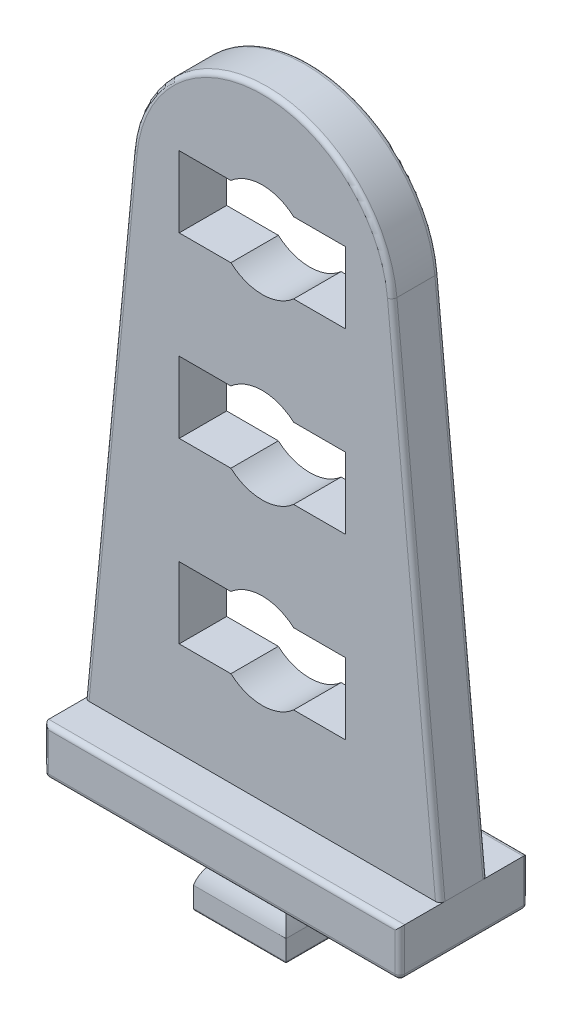
SolidWorks part; units mm, degrees
ref_plane "前视基准面" through (0, 0, 0) normal (0, 0, 1) x (1, 0, 0)
ref_plane "上视基准面" through (0, 0, 0) normal (0, 1, 0) x (1, 0, 0)
ref_plane "右视基准面" through (0, 0, 0) normal (1, 0, 0) x (0, 0, -1)
sketch "草图1" plane through (0, 0, 0) normal (0, 0, 1) x (1, 0, 0)
  line L0 (0, 0) -> (7.5, 0)
  line L1 (7.5, 0) -> (7.5, 2)
  line L2 (7.5, 2) -> (-7.5, 2)
  line L3 (-7.5, 2) -> (-7.5, 0)
  line L4 (-7.5, 0) -> (0, 0)
  dimension "D1" = 7.5
  dimension "D2" = 15
  dimension "D3" = 2
extrude "凸台-拉伸1" add sketch "草图1" along normal blind 2.7 and the other way blind 2.7
sketch "草图2" plane through (0, 0, 0) normal (0, 0, 1) x (1, 0, 0)
  line L0 (0, 2) -> (0, 7.5) construction
  line L1 (7.5, 2) -> (-7.5, 2) construction
  line L2 (0, 7.5) -> (0, 15) construction
  line L3 (0, 15) -> (0, 22.5) construction
  line L4 (0, 22.5) -> (0, 28) construction
  line L5 (-7.5, 2) -> (-5.4747, 23.0273)
  line L6 (-7.5, 2) -> (7.5, 2)
  line L7 (7.5, 2) -> (5.4747, 23.0273)
  arc A0 (5.4747, 23.0273) -> (-5.4747, 23.0273) centre (0, 22.5) ccw
  dimension "D1" = 5.5
  dimension "D2" = 7.5
  dimension "D3" = 7.5
  dimension "D4" = 5.5
extrude "凸台-拉伸2" add sketch "草图2" along normal blind 1 and the other way blind 1
sketch "草图3" plane through (0, 0, 1) normal (0, 0, 1) x (1, 0, 0)
  line L0 (0, 0) -> (0, 7.5) construction
  line L1 (3.5, 6) -> (3.5, 9)
  line L2 (3.5, 6) -> (1.3229, 6)
  line L3 (3.5, 9) -> (1.3229, 9)
  line L4 (-3.5, 6) -> (-3.5, 9)
  line L5 (3.5, 6) -> (-3.5, 9) construction
  line L6 (3.5, 9) -> (-3.5, 6) construction
  line L7 (-1.3229, 9) -> (-3.5, 9)
  line L8 (-1.3229, 6) -> (-3.5, 6)
  arc A0 (-1.3229, 6) -> (1.3229, 6) centre (0, 7.5) ccw
  arc A1 (1.3229, 9) -> (-1.3229, 9) centre (0, 7.5) ccw
  dimension "D2" = 4
  dimension "D1" = 7.5
  dimension "D3" = 3
  dimension "D4" = 7
extrude "切除-拉伸1" cut sketch "草图3" against normal through all
pattern_linear "阵列(线性)1" count 3 spacing 7.5 along (0, 1, 0) of "切除-拉伸1"
sketch "草图4" plane through (0, 0, 0) normal (0, 0, 1) x (1, 0, 0)
  line L0 (0, 0) -> (0, -2) construction
  line L1 (0, -2) -> (0, -2.5) construction
  line L2 (1.5, 0) -> (-1.5, 0)
  line L3 (-7.5, 0) -> (7.5, 0) construction
  line L4 (-1.5, 0) -> (-1.5, -0.6771)
  line L5 (1.95, -2.5) -> (-1.95, -2.5)
  line L6 (-1.95, -2.5) -> (-1.95, -1.5556)
  line L7 (1.95, -2.5) -> (1.95, -1.5556)
  line L8 (1.5, 0) -> (1.5, -0.6771)
  arc A0 (-1.5, -0.6771) -> (-1.95, -1.5556) centre (0, -2) ccw
  arc A1 (1.5, -0.6771) -> (1.95, -1.5556) centre (0, -2) cw
  dimension "D1" = 2
  dimension "D2" = 0.5
  dimension "D3" = 1.5
  dimension "D4" = 1.95
extrude "凸台-拉伸3" add sketch "草图4" along normal blind 2 and the other way blind 2
sketch "草图5" plane through (0, 0, 0) normal (1, 0, 0) x (0, 0, -1)
  line L0 (0, 0) -> (0, -2) construction
  line L1 (0, -2) -> (0, -2.5) construction
  line L2 (2, -2.5) -> (-2, -2.5) construction
  line L3 (0, 0) -> (1.5, 0) construction
  line L4 (1.5, 0) -> (1.5, -0.6771)
  line L5 (0, -2.5) -> (1.95, -2.5) construction
  line L6 (1.95, -2.5) -> (1.95, -1.5556)
  line L7 (1.95, -2.5) -> (2, -2.5)
  line L8 (2, -2.5) -> (2, 0)
  line L9 (2, 0) -> (1.5, 0)
  line L10 (-2, 0) -> (-1.5, 0)
  line L11 (-1.5, 0) -> (-1.5, -0.6771)
  line L12 (-2, -2.5) -> (-2, 0)
  line L13 (-1.95, -2.5) -> (-1.95, -1.5556)
  line L14 (-1.95, -2.5) -> (-2, -2.5)
  arc A0 (1.95, -1.5556) -> (1.5, -0.6771) centre (0, -2) ccw
  arc A1 (-1.95, -1.5556) -> (-1.5, -0.6771) centre (0, -2) cw
  dimension "D1" = 2
  dimension "D2" = 1.5
  dimension "D3" = 1.95
extrude "切除-拉伸2" cut sketch "草图5" against normal blind 2 and the other way blind 2
fillet "圆角1" radius 0.1 4 edges at (0, -2.5, -1.95) (-1.95, -2.5, 0) (0, -2.5, 1.95) (1.95, -2.5, 0)
fillet "圆角4" radius 0.2 8 edges at (-7.5, 1, 2.7) (0, 2, 2.7) (7.5, 1, 2.7) (0, 0, 2.7) (7.5, 1, -2.7) (0, 2, -2.7) (-7.5, 1, -2.7) (0, 0, -2.7)
fillet "圆角5" radius 0.2 6 edges at (-7.4414, 0.0586, -2.6414) (-7.4414, 0.0586, 2.6414) (7.4414, 0.0586, -2.6414) (7.4414, 0.0586, 2.6414) (-7.5, 0, 0) (7.5, 0, 0)
fillet "圆角8" radius 0.2 6 edges at (0, 28, -1) (0, 28, 1)
